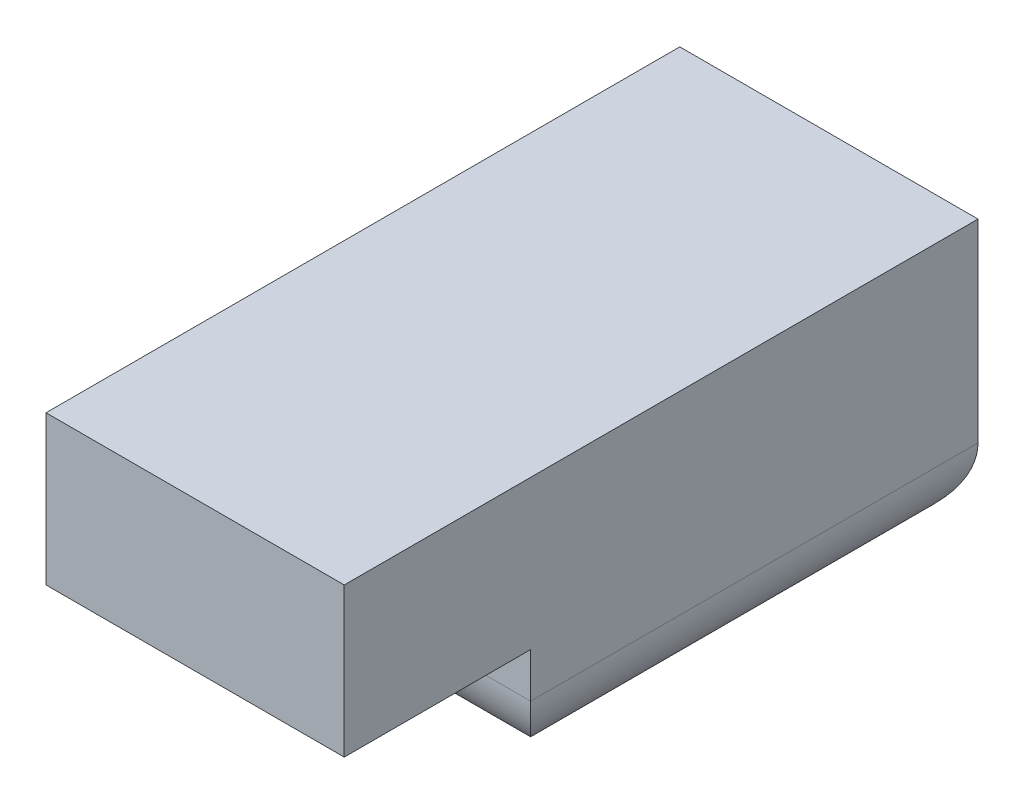
SolidWorks part; units mm, degrees
ref_plane "Front Plane" through (0, 0, 0) normal (0, 0, 1) x (1, 0, 0)
ref_plane "Top Plane" through (0, 0, 0) normal (0, 1, 0) x (1, 0, 0)
ref_plane "Right Plane" through (0, 0, 0) normal (1, 0, 0) x (0, 0, -1)
ref_axis "X-Axis" through (-88.99, 0, 0) along (1, 0, 0)
ref_axis "Y-Axis" through (0, 55, 0) along (0, -1, 0)
ref_axis "Z-Axis" through (0, 0, -88.99) along (0, 0, 1)
sketch "Sketch2" plane through (0, 0, 0) normal (0, 1, 0) x (1, 0, 0)
  line L1 (-2, -4.25) -> (2, -4.25)
  line L2 (-2, -4.25) -> (-2, 4.25)
  line L3 (-2, 4.25) -> (2, 4.25)
  line L4 (2, -4.25) -> (2, 4.25)
  line L5 (-2, -4.25) -> (2, 4.25) construction
  line L6 (-2, 4.25) -> (2, -4.25) construction
  point P0 (0, 0)
  dimension "D1" = 8.5
  dimension "D2" = 4
extrude "Boss-Extrude1" add sketch "Sketch2" along normal blind 2
sketch "Sketch3" plane through (0, 0, 0) normal (0, -1, 0) x (1, 0, 0)
  line L0 (2, 4.25) -> (2, -4.25) construction
  line L1 (-2, -4.25) -> (2, -4.25)
  line L2 (-2, -4.25) -> (-2, 1.75)
  line L3 (-2, 1.75) -> (2, 1.75)
  line L4 (2, -4.25) -> (2, 1.75)
  dimension "D1" = 6
extrude "Boss-Extrude2" add sketch "Sketch3" along normal blind 1.6
fillet "Fillet1" radius 1 4 edges at (-2, -1.6, -1.25) (0, -1.6, -4.25) (2, -1.6, -1.25) (0, -1.6, 1.75)
